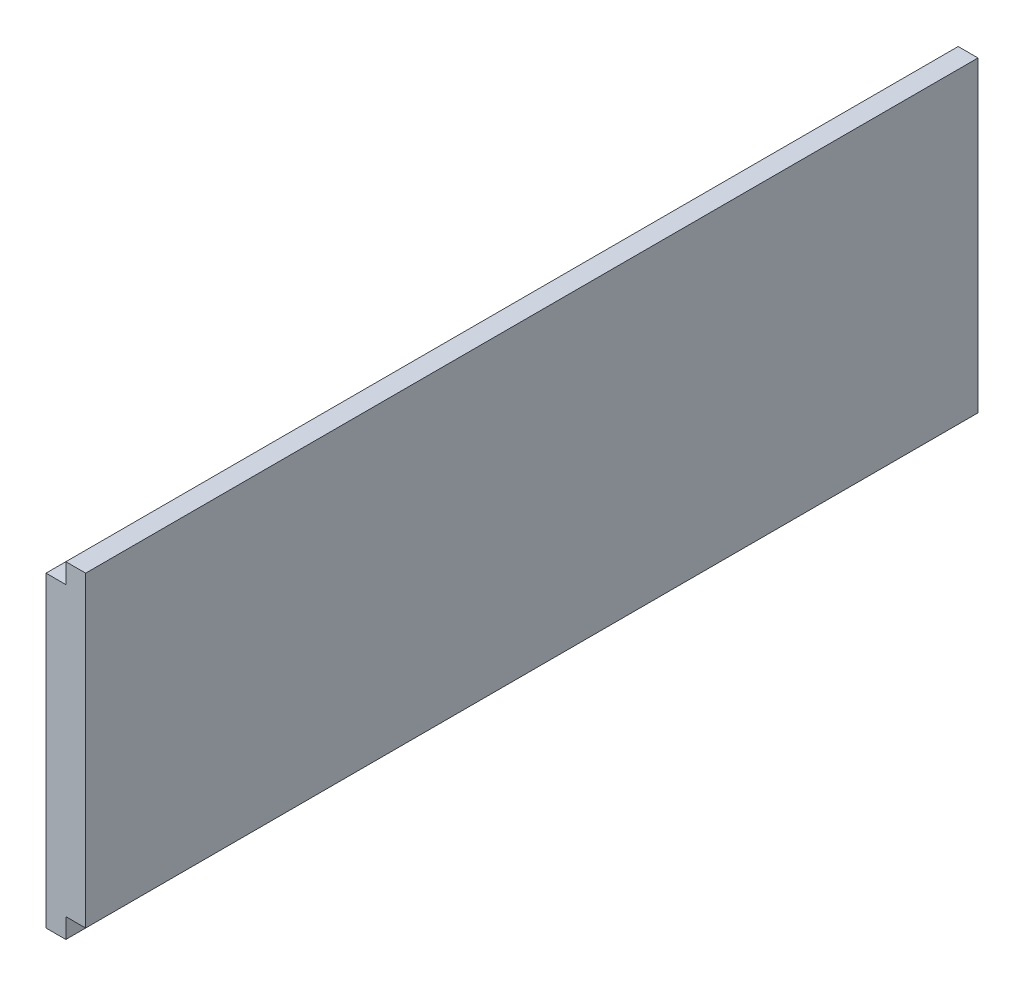
SolidWorks part; units mm, degrees
material "Сосна"
ref_plane "Спереди" through (0, 0, 0) normal (0, 0, 1) x (1, 0, 0)
ref_plane "Сверху" through (0, 0, 0) normal (0, 1, 0) x (1, 0, 0)
ref_plane "Справа" through (0, 0, 0) normal (1, 0, 0) x (0, 0, -1)
sketch "Эскиз1" plane through (0, 0, 0) normal (0, 0, 1) x (1, 0, 0)
  line L0 (0, 0) -> (0, 155)
  line L1 (0, 155) -> (10, 155)
  line L2 (10, 155) -> (10, 165)
  line L3 (10, 165) -> (20, 165)
  line L4 (20, 165) -> (20, 10)
  line L5 (20, 10) -> (10, 10)
  line L6 (10, 10) -> (10, 0)
  line L7 (10, 0) -> (0, 0)
  dimension "D1" = 155
  dimension "D2" = 10
  dimension "D3" = 10
  dimension "D4" = 20
  dimension "D5" = 10
  dimension "D6" = 10
extrude "Бобышка-Вытянуть1" add sketch "Эскиз1" along normal blind 450
